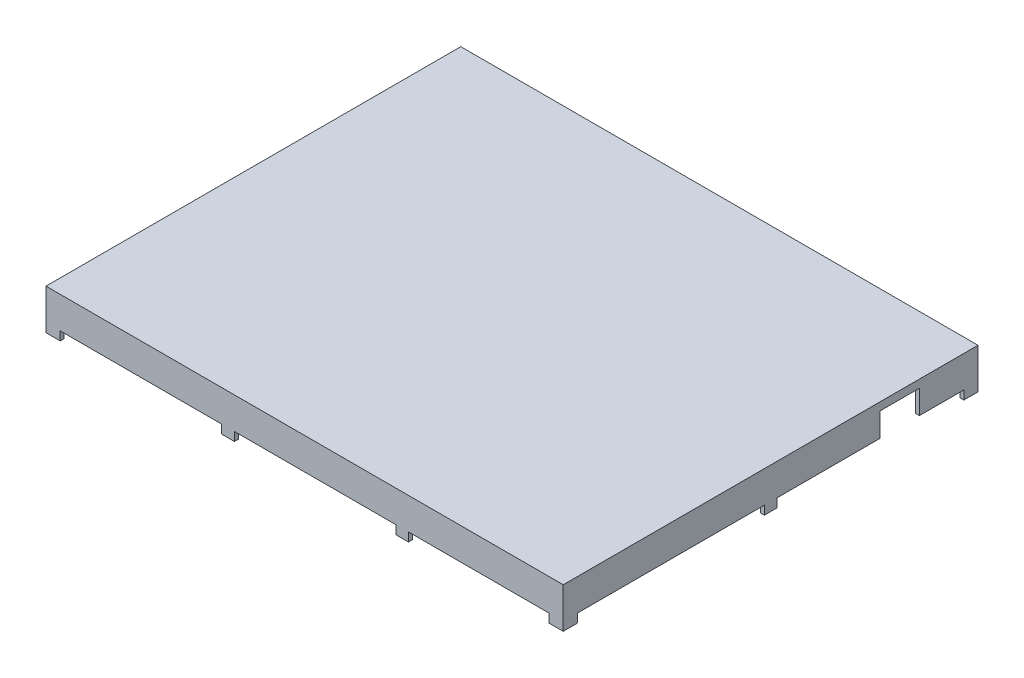
SolidWorks part; units mm, degrees
material "6061 合金"
ref_plane "前视基准面" through (0, 0, 0) normal (0, 0, 1) x (1, 0, 0)
ref_plane "上视基准面" through (0, 0, 0) normal (0, 1, 0) x (1, 0, 0)
ref_plane "右视基准面" through (0, 0, 0) normal (1, 0, 0) x (0, 0, -1)
other "Configuration Table"
sketch "草图1" plane through (0, 0, 0) normal (0, 1, 0) x (1, 0, 0)
  line L1 (0, 0) -> (65.34, 0)
  line L2 (0, 0) -> (0, 52.4)
  line L3 (0, 52.4) -> (65.34, 52.4)
  line L4 (65.34, 0) -> (65.34, 52.4)
  line L5 (0.5, 0.5) -> (64.84, 0.5)
  line L6 (0.5, 0.5) -> (0.5, 51.9)
  line L7 (0.5, 51.9) -> (64.84, 51.9)
  line L8 (64.84, 0.5) -> (64.84, 51.9)
  dimension "D1" = 65.34
  dimension "D2" = 52.4
extrude "凸台-拉伸2" add sketch "草图1" along normal blind 5.1 contours L2 L3 L4 L1
extrude "切除-拉伸2" cut sketch "草图1<5>" along normal blind 4.6 contours L6 L7 L8 L5
sketch "草图1<5>" plane through (0, 0, 0) normal (0, 1, 0) x (1, 0, 0) same geometry as "草图1"
sketch "草图2" plane through (0, 0, 0) normal (0, 0, 1) x (1, 0, 0)
  line L0 (0, 0) -> (1.8, 0)
  line L1 (0.5, 0) -> (64.84, 0) construction
  line L2 (1.8, 0) -> (1.8, 1.1)
  line L3 (1.8, 1.1) -> (22.2, 1.1)
  line L4 (22.2, 1.1) -> (22.2, 0)
  line L5 (22.2, 0) -> (23.8, 0)
  line L6 (23.8, 0) -> (23.8, 1.1)
  line L7 (23.8, 1.1) -> (44.19, 1.1)
  line L8 (44.19, 1.1) -> (44.19, 0)
  line L9 (44.19, 0) -> (45.79, 0)
  line L10 (45.79, 0) -> (45.79, 1.1)
  line L11 (45.79, 1.1) -> (63.54, 1.1)
  line L12 (63.54, 1.1) -> (63.54, 0)
  line L13 (63.54, 0) -> (65.34, 0)
  line L14 (1.8, 0) -> (22.2, 0)
  line L15 (23.8, 0) -> (44.19, 0)
  line L16 (45.79, 0) -> (63.54, 0)
  dimension "D1" = 1.1
  dimension "D2" = 1.1
  dimension "D3" = 1.1
  dimension "D4" = 1.8
  dimension "D5" = 1.8
  dimension "D6" = 1.6
  dimension "D7" = 1.6
  dimension "D8" = 20.4
  dimension "D9" = 17.75
sketch "草图3" plane through (0, 0, 0) normal (0, 0, 1) x (1, 0, 0)
  line L0 (1.8, 0) -> (22.2, 0)
  line L1 (23.8, 0) -> (44.19, 0)
  line L2 (45.79, 0) -> (63.54, 0)
extrude "切除-拉伸3" cut sketch "草图2" against normal blind 56.4 contours L6 L7 L8 L15 | L2 L3 L4 L14 | L12 L11 L10 L16
sketch "草图4" plane through (65.34, 0, 0) normal (1, 0, 0) x (0, 0, -1)
  line L0 (0, 0) -> (1.8, 0)
  line L1 (0.5, 0) -> (51.9, 0) construction
  line L2 (1.8, 0) -> (1.8, 1.1)
  line L3 (1.8, 1.1) -> (25.4, 1.1)
  line L4 (25.4, 1.1) -> (25.4, 0)
  line L5 (25.4, 0) -> (27, 0)
  line L6 (27, 0) -> (27, 1.1)
  line L7 (27, 1.1) -> (40, 1.1)
  line L8 (40, 1.1) -> (40, 4.1)
  line L9 (40, 4.1) -> (45, 4.1)
  line L10 (45, 4.1) -> (45, 1.1)
  line L11 (45, 1.1) -> (50.6, 1.1)
  line L12 (50.6, 1.1) -> (50.6, 0)
  line L13 (50.6, 0) -> (52.4, 0)
  dimension "D1" = 1.8
  dimension "D2" = 1.6
  dimension "D3" = 5
  dimension "D4" = 1.8
  dimension "D5" = 5.6
  dimension "D6" = 23.6
  dimension "D7" = 1.1
  dimension "D8" = 1.1
  dimension "D9" = 1.1
  dimension "D10" = 3
sketch "草图5" plane through (65.34, 0, 0) normal (1, 0, 0) x (0, 0, -1)
  line L0 (1.8, 0) -> (25.4, 0)
  line L1 (27, 0) -> (50.6, 0)
sketch "草图9" plane through (65.34, 0, 0) normal (1, 0, 0) x (0, 0, -1)
  line L0 (1.8, 0) -> (25.4, 0)
  line L1 (27, 0) -> (50.6, 0)
  line L2 (1.8, 0) -> (1.8, 1.1)
  line L3 (1.8, 1.1) -> (25.4, 1.1)
  line L4 (25.4, 1.1) -> (25.4, 0)
  line L5 (27, 0) -> (27, 1.1)
  line L6 (27, 1.1) -> (40, 1.1)
  line L7 (40, 1.1) -> (40, 4.1)
  line L8 (40, 4.1) -> (45, 4.1)
  line L9 (45, 4.1) -> (45, 1.1)
  line L10 (45, 1.1) -> (50.6, 1.1)
  line L11 (50.6, 1.1) -> (50.6, 0)
extrude "切除-拉伸4" cut sketch "草图9" against normal blind 4.9
sketch "草图11" plane through (0, 0, 0) normal (-1, 0, 0) x (0, 0, 1)
  line L0 (-52.4, 0) -> (-50.6, 0)
  line L1 (-50.6, 0) -> (-50.6, 1.1)
  line L2 (0, 0) -> (-1.8, 0)
  line L3 (-1.8, 0) -> (-1.8, 1.1)
  line L4 (-1.8, 1.1) -> (-18.8, 1.1)
  line L5 (-1.8, 1.1) -> (-25.4, 1.1) construction
  line L6 (-18.8, 1.1) -> (-18.8, 4.1)
  line L8 (-18.8, 4.1) -> (-41.77, 4.1)
  line L9 (-41.77, 1.1) -> (-50.6, 1.1)
  line L10 (-40, 4.1) -> (-45, 4.1) construction
  line L11 (-41.77, 4.1) -> (-41.77, 1.1)
  line L12 (-50.6, 0) -> (-1.8, 0)
  dimension "D1" = 1.8
  dimension "D2" = 8.83
  dimension "D3" = 17
sketch "草图12" plane through (0, 0, 0) normal (-1, 0, 0) x (0, 0, 1)
  line L0 (-50.6, 0) -> (-1.8, 0)
sketch "草图13" plane through (0, 0, 0) normal (-1, 0, 0) x (0, 0, 1)
  line L0 (-50.6, 0) -> (-50.6, 1.1)
  line L1 (-50.6, 1.1) -> (-41.77, 1.1)
  line L2 (-41.77, 1.1) -> (-41.77, 4.1)
  line L3 (-41.77, 4.1) -> (-18.8, 4.1)
  line L4 (-18.8, 4.1) -> (-18.8, 1.1)
  line L5 (-18.8, 1.1) -> (-1.8, 1.1)
  line L6 (-1.8, 1.1) -> (-1.8, 0)
  line L7 (-1.8, 0) -> (-50.6, 0)
extrude "切除-拉伸6" cut sketch "草图13" against normal blind 4.9
sketch "草图14" plane through (0, 5.1, 0) normal (0, 1, 0) x (1, 0, 0)
  line L0 (65.34, 0) -> (65.34, 52.4) construction
  text T0 "可重构超高频物联网端机\r\n电子科技大学CRFICS\r\n" font "楷体" height 3.5
  dimension "D1" = 65.34
